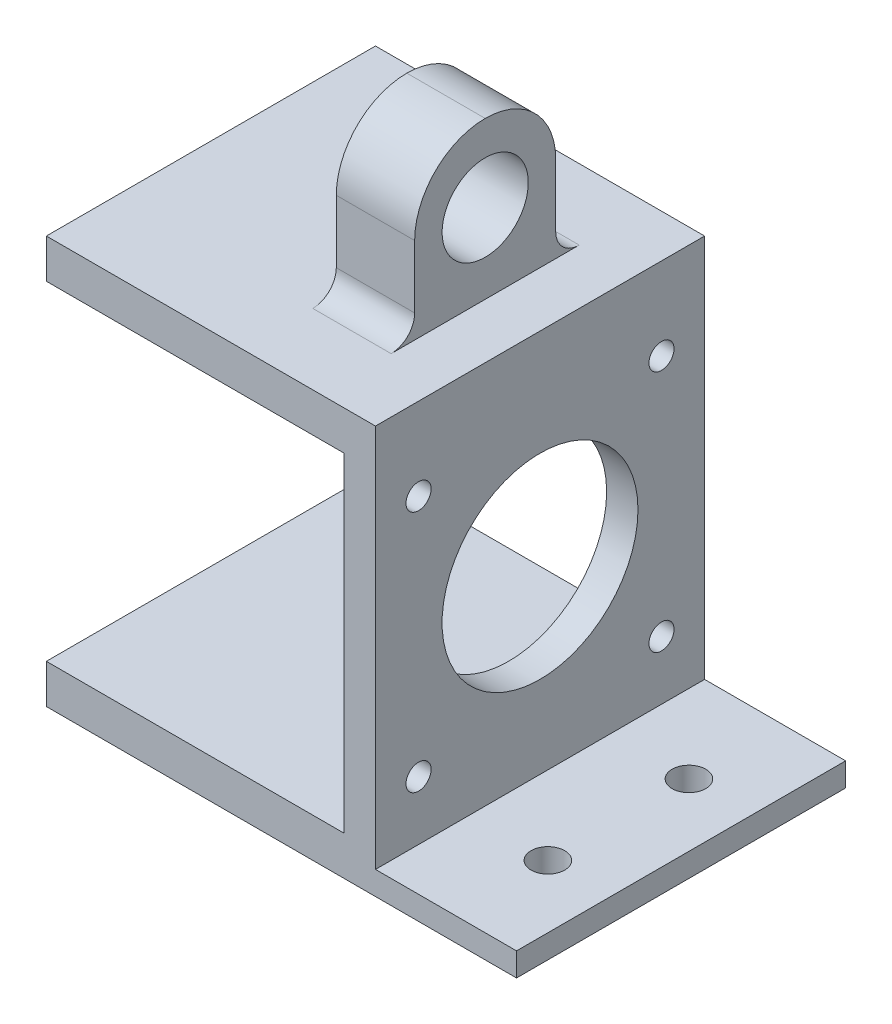
SolidWorks part; units mm, degrees
ref_plane "Front Plane" through (0, 0, 0) normal (0, 0, 1) x (1, 0, 0)
ref_plane "Top Plane" through (0, 0, 0) normal (0, 1, 0) x (1, 0, 0)
ref_plane "Right Plane" through (0, 0, 0) normal (1, 0, 0) x (0, 0, -1)
sketch "Sketch1" plane through (0, 0, 0) normal (0, 1, 0) x (1, 0, 0)
  line L1 (0, 0) -> (94, 0)
  line L2 (0, 0) -> (0, -42)
  line L3 (0, -42) -> (94, -42)
  line L4 (94, 0) -> (94, -42)
  dimension "D1" = 94
  dimension "D2" = 42
extrude "Boss-Extrude1" add sketch "Sketch1" along normal blind 3
sketch "Sketch2" plane through (0, 0, 0) normal (0, -1, 0) x (1, 0, 0)
  line L0 (94, 0) -> (0, 0) construction
  line L1 (0, 42) -> (4, 42)
  line L2 (0, 42) -> (0, 0)
  line L3 (0, 0) -> (4, 0)
  line L4 (4, 42) -> (4, 0)
  line L6 (94, 42) -> (90, 42)
  line L7 (94, 42) -> (94, 0)
  line L8 (94, 0) -> (90, 0)
  line L9 (90, 42) -> (90, 0)
  dimension "D1" = 4
  dimension "D2" = 4
extrude "Boss-Extrude2" add sketch "Sketch2" against normal blind 47
sketch "Sketch3" plane through (94, 0, 0) normal (1, 0, 0) x (0, 0, -1)
  circle B0 centre (-21, 26) radius 12.5
  circle B1 centre (-36.5, 41.5) radius 1.6
  circle B2 centre (-5.5, 41.5) radius 1.6
  circle B3 centre (-36.5, 10.5) radius 1.6
  circle B4 centre (-5.5, 10.5) radius 1.6
sketch_block_instance "stepper mounting hole pattern-1"
sketch_block "stepper mounting hole pattern" parameters "D1"=25, "D2"=3.2, "D3"=3.2, "D4"=3.2, "D5"=3.2
extrude "Cut-Extrude1" cut sketch "Sketch3" against normal through all
sketch "Sketch4" plane through (94, 0, 0) normal (1, 0, 0) x (0, 0, -1)
  line L0 (0, 47) -> (0, 0) construction
  line L1 (-42, 0) -> (0, 0)
  line L2 (-42, 0) -> (-42, 5)
  line L3 (-42, 5) -> (0, 5)
  line L4 (0, 0) -> (0, 5)
  dimension "D1" = 5
extrude "Boss-Extrude3" add sketch "Sketch4" along normal blind 40
sketch "Sketch5" plane through (0, 0, 0) normal (-1, 0, 0) x (0, 0, 1)
  line L0 (42, 47) -> (42, 0) construction
  line L1 (0, 0) -> (42, 0)
  line L2 (0, 0) -> (0, 5)
  line L3 (0, 5) -> (42, 5)
  line L4 (42, 0) -> (42, 5)
  dimension "D1" = 5
extrude "Boss-Extrude4" add sketch "Sketch5" along normal blind 38
sketch "Sketch7" plane through (0, 47, 0) normal (0, 1, 0) x (1, 0, 0)
  line L0 (-38, -42) -> (0, -42) construction
  line L1 (4, 0) -> (-38, 0)
  line L2 (4, 0) -> (4, -42)
  line L3 (4, -42) -> (-38, -42)
  line L4 (-38, 0) -> (-38, -42)
  line L5 (134, -42) -> (94, -42) construction
  line L6 (90, 0) -> (134, 0)
  line L7 (90, 0) -> (90, -42)
  line L8 (90, -42) -> (134, -42)
  line L9 (134, 0) -> (134, -42)
extrude "Boss-Extrude6" add sketch "Sketch7" along normal blind 5
sketch "Sketch9" plane through (0, 3, 0) normal (0, 1, 0) x (1, 0, 0)
  line L0 (4, -42) -> (90, -42) construction
  line L1 (90, 0) -> (90, -42) construction
  line L2 (90, 0) -> (4, 0) construction
  line L3 (4, -42) -> (4, 0) construction
  circle A0 centre (83, -20) radius 2.15
  circle A1 centre (65, -20) radius 2.15
  circle A2 centre (74, -11) radius 2.15
  circle A3 centre (74, -29) radius 2.15
  circle A4 centre (14, -12) radius 2.15
  circle A5 centre (14, -30) radius 2.15
  circle A6 centre (30, -12) radius 2.15
  circle A7 centre (30, -30) radius 2.15
  point P24 (0, 0)
  point P25 (0, 0)
  point P26 (0, 0)
  point P27 (0, 0)
  dimension "D1" = 4.3
  dimension "D2" = 22
  dimension "D3" = 7
  dimension "D4" = 18
  dimension "D5" = 9
  dimension "D6" = 18
  dimension "D7" = 9
  dimension "D8" = 18
  dimension "D9" = 12
  dimension "D10" = 10
  dimension "D11" = 16
extrude "Cut-Extrude2" cut sketch "Sketch9" against normal through all
sketch "Sketch11" plane through (0, 52, 0) normal (0, 1, 0) x (1, 0, 0)
  line L0 (4, -42) -> (4, 0) construction
  line L1 (-13, -12) -> (-3, -12)
  line L2 (-13, -12) -> (-13, -30)
  line L3 (-13, -30) -> (-3, -30)
  line L4 (-3, -12) -> (-3, -30)
  line L5 (4, 0) -> (-38, 0) construction
  line L7 (102, -12) -> (112, -12)
  line L8 (102, -12) -> (102, -30)
  line L9 (102, -30) -> (112, -30)
  line L10 (112, -12) -> (112, -30)
  line L11 (90, 0) -> (90, -42) construction
  dimension "D1" = 10
  dimension "D2" = 7
  dimension "D3" = 18
  dimension "D4" = 12
  dimension "D5" = 18
  dimension "D6" = 10
  dimension "D7" = 12
extrude "Boss-Extrude7" add sketch "Sketch11" along normal blind 20
sketch "Sketch13" plane through (-13, 0, 0) normal (-1, 0, 0) x (0, 0, 1)
  line L0 (0, 0) -> (42, 0) construction
  line L1 (12, 72) -> (12, 52) construction
  circle A0 centre (21, 62.15) radius 5.5
  dimension "D2" = 11
  dimension "D1" = 62.15
  dimension "D3" = 9
extrude "Cut-Extrude3" cut sketch "Sketch13" against normal through all
sketch "Sketch20" plane through (0, 0, 42) normal (0, 0, 1) x (1, 0, 0)
  line L0 (134, 0) -> (134, 52)
  line L1 (134, 52) -> (90, 52)
  line L2 (90, 52) -> (90, 0)
  line L3 (-38, 0) -> (134, 0) construction
  line L4 (90, 0) -> (95, 0)
  line L5 (95, 0) -> (95, 20)
  line L6 (95, 20) -> (102, 26)
  line L7 (102, 26) -> (112, 26)
  line L8 (112, 26) -> (129, 20)
  line L9 (129, 20) -> (129, 0)
  line L10 (129, 0) -> (134, 0)
  dimension "D1" = 5
  dimension "D2" = 5
  dimension "D3" = 10
  dimension "D4" = 7
  dimension "D5" = 20
  dimension "D6" = 6
extrude "Boss-Extrude11" add sketch "Sketch20" along normal blind 5
sketch "Sketch23" plane through (0, 0, 47) normal (0, 0, 1) x (1, 0, 0)
  line L0 (134, 52) -> (90, 52) construction
  line L1 (102, 52) -> (112, 52)
  line L2 (102, 52) -> (102, 26)
  line L3 (102, 26) -> (112, 26)
  line L4 (112, 52) -> (112, 26)
  line L5 (102, 52) -> (112, 52) construction
extrude "Boss-Extrude12" add sketch "Sketch23" along normal blind 50
sketch "Sketch24" plane through (112, 0, 0) normal (1, 0, 0) x (0, 0, -1)
  line L0 (-47, 26) -> (-97, 39)
  line L1 (-97, 26) -> (-97, 52) construction
  line L2 (-97, 39) -> (-97, 26)
  line L3 (-97, 26) -> (-47, 26)
extrude "Cut-Extrude7" cut sketch "Sketch24" against normal through all
sketch "Sketch25" plane through (0, 52, 0) normal (0, 1, 0) x (1, 0, 0)
  line L0 (102, -97) -> (102, -47) construction
  line L1 (102, -62) -> (112, -62)
  line L2 (102, -62) -> (102, -80)
  line L3 (102, -80) -> (112, -80)
  line L4 (112, -62) -> (112, -80)
  line L5 (112, -97) -> (112, -47) construction
  line L6 (102, -30) -> (112, -30) construction
  dimension "D1" = 18
  dimension "D2" = 32
extrude "Boss-Extrude13" add sketch "Sketch25" along normal blind 20
sketch "Sketch26" plane through (112, 0, 0) normal (1, 0, 0) x (0, 0, -1)
  line L0 (-80, 72) -> (-80, 52) construction
  line L1 (-47, 0) -> (0, 0) construction
  circle A0 centre (-71, 62.15) radius 5.5
  dimension "D1" = 11
  dimension "D2" = 9
  dimension "D3" = 62.15
extrude "Cut-Extrude8" cut sketch "Sketch26" against normal through all
sketch "Sketch27" plane through (0, 3, 0) normal (0, 1, 0) x (1, 0, 0)
  line L0 (90, 0) -> (90, -42) construction
  line L1 (41, -12) -> (53, -12)
  line L2 (41, -12) -> (41, -30)
  line L3 (41, -30) -> (53, -30)
  line L4 (53, -12) -> (53, -30)
  line L5 (4, -42) -> (90, -42) construction
  dimension "D1" = 37
  dimension "D2" = 18
  dimension "D3" = 12
  dimension "D4" = 12
extrude "Boss-Extrude14" add sketch "Sketch27" along normal blind 69
sketch "Sketch28" plane through (53, 0, 0) normal (1, 0, 0) x (0, 0, -1)
  line L0 (-12, 72) -> (-12, 3) construction
  line L1 (-47, 0) -> (0, 0) construction
  circle A0 centre (-21, 62.15) radius 5.5
  dimension "D1" = 11
  dimension "D2" = 9
  dimension "D3" = 62.15
extrude "Cut-Extrude10" cut sketch "Sketch28" against normal blind 5
sketch "Sketch29" plane through (41, 0, 0) normal (-1, 0, 0) x (0, 0, 1)
  line L0 (30, 72) -> (30, 3) construction
  line L2 (0, 0) -> (42, 0) construction
  circle A0 centre (21, 62.15) radius 5.5
  dimension "D2" = 11
  dimension "D1" = 9
  dimension "D3" = 62.15
extrude "Cut-Extrude11" cut sketch "Sketch29" against normal blind 5
fillet "Fillet4" radius 9 8 edges at (-8, 72, 12) (-8, 72, 30) (107, 72, 12) (107, 72, 30) (107, 72, 62) (107, 72, 80) (47, 72, 12) (47, 72, 30)
fillet "Fillet3" radius 3 14 edges at (-8, 52, 12) (-8, 52, 30) (107, 52, 12) (107, 52, 30) (107, 52, 62) (107, 52, 80) (129, 20, 44.5) (112, 26, 44.5) (102, 26, 44.5) (95, 20, 44.5) (107, 52, 97) (107, 39, 97) (47, 3, 12) (47, 3, 30)
sketch "Sketch30" plane through (0, 0, 0) normal (0, -1, 0) x (1, 0, 0)
  line L1 (22, 120) -> (134, 120)
  line L2 (22, 120) -> (22, 0)
  line L3 (22, 0) -> (134, 0)
  line L4 (134, 120) -> (134, 0)
  line L5 (-38, 0) -> (-38, 42) construction
  point P9 (0, 0)
  dimension "D1" = 60
  dimension "D2" = 120
extrude "Cut-Extrude13" cut sketch "Sketch30" against normal through all
